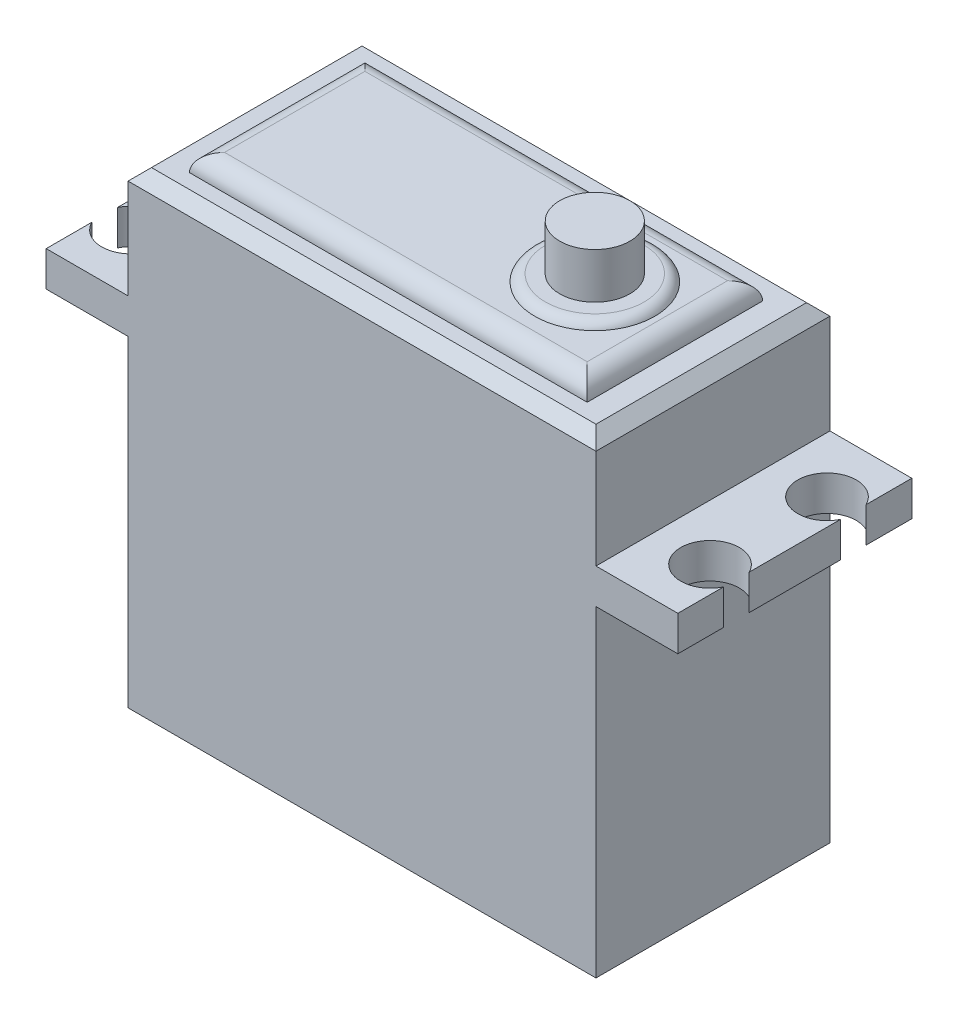
SolidWorks part; units mm, degrees
ref_plane "前视基准面" through (0, 0, 0) normal (0, 0, 1) x (1, 0, 0)
ref_plane "上视基准面" through (0, 0, 0) normal (0, 1, 0) x (1, 0, 0)
ref_plane "右视基准面" through (0, 0, 0) normal (1, 0, 0) x (0, 0, -1)
sketch "草图1" plane through (0, 0, 0) normal (0, 1, 0) x (1, 0, 0)
  line L1 (0, 0) -> (40, 0)
  line L2 (0, 0) -> (0, -20)
  line L3 (0, -20) -> (40, -20)
  line L4 (40, 0) -> (40, -20)
  dimension "D1" = 40
  dimension "D2" = 20
extrude "凸台-拉伸1" add sketch "草图1" along normal blind 40
sketch "草图2" plane through (0, 40, 0) normal (0, 1, 0) x (1, 0, 0)
  line L1 (0, 0) -> (0, -20) construction
  line L2 (40, 0) -> (0, 0) construction
  circle A0 centre (29.9, -10) radius 3
  dimension "D1" = 6
  dimension "D2" = 29.9
  dimension "D3" = 10
sketch "草图7" plane through (0, 0, 0) normal (0, -1, 0) x (1, 0, 0)
  line L0 (40, 20) -> (47, 20)
  line L1 (40, 20) -> (40, 0) construction
  line L2 (47, 0) -> (40, 0)
  line L3 (47, 13.9103) -> (47, 6.0897)
  line L4 (47, 20) -> (47, 16.0897)
  line L6 (47, 3.9103) -> (47, 0)
  line L7 (40, 20) -> (40, 0)
  line L8 (20, 27.4914) -> (20, -7.6686) construction
  line L9 (0, 0) -> (0, 20) construction
  line L10 (0, 20) -> (0, 0)
  line L11 (-7, 3.9103) -> (-7, 0)
  line L12 (-7, 20) -> (-7, 16.0897)
  line L13 (-7, 13.9103) -> (-7, 6.0897)
  line L14 (-7, 0) -> (0, 0)
  line L15 (0, 20) -> (-7, 20)
  arc A2 (47, 16.0897) -> (47, 13.9103) centre (44.75, 15) ccw
  arc A3 (47, 6.0897) -> (47, 3.9103) centre (44.75, 5) ccw
  arc A4 (-7, 6.0897) -> (-7, 3.9103) centre (-4.75, 5) cw
  arc A5 (-7, 16.0897) -> (-7, 13.9103) centre (-4.75, 15) cw
  dimension "D2" = 10
  dimension "D3" = 5
  dimension "D4" = 5
  dimension "D5" = 5
  dimension "D1" = 7
  dimension "D6" = 4.75
  dimension "D7" = 4.75
  dimension "D8" = 35.16
  dimension "D9" = 20
extrude "凸台-拉伸4" add sketch "草图7" against normal blind 3 from offset 27.5 offset against normal yes
extrude "凸台-拉伸5" add sketch "草图2" along normal blind 6 contours A0
sketch "草图8" plane through (0, 40, 0) normal (0, 1, 0) x (1, 0, 0)
  line L1 (3, -17.7516) -> (37, -17.7516)
  line L2 (3, -17.7516) -> (3, -2.7516)
  line L3 (3, -2.7516) -> (37, -2.7516)
  line L4 (37, -17.7516) -> (37, -2.7516)
  line L6 (40, -20) -> (40, 0) construction
  line L7 (40, 0) -> (0, 0) construction
  dimension "D1" = 15
  dimension "D2" = 34
  dimension "D3" = 3
  dimension "D4" = 2.7516
extrude "凸台-拉伸6" add sketch "草图8" along normal blind 1.5
fillet "圆角1" radius 1.5 4 edges at (20, 41.5, 2.7516) (37, 41.5, 10.2516) (20, 41.5, 17.7516) (3, 41.5, 10.2516)
sketch "草图9" plane through (0, 41.5, 0) normal (0, 1, 0) x (1, 0, 0)
  circle A0 centre (29.9, -10) radius 5.1303
extrude "凸台-拉伸7" add sketch "草图9" along normal blind 0.6
fillet "圆角2" radius 1 1 edges at (29.9, 42.1, 15.1303)
chamfer "倒角1" distance 1 angle 45 4 edges at (0, 40, 10) (20, 40, 20) (40, 40, 10) (20, 40, 0)
